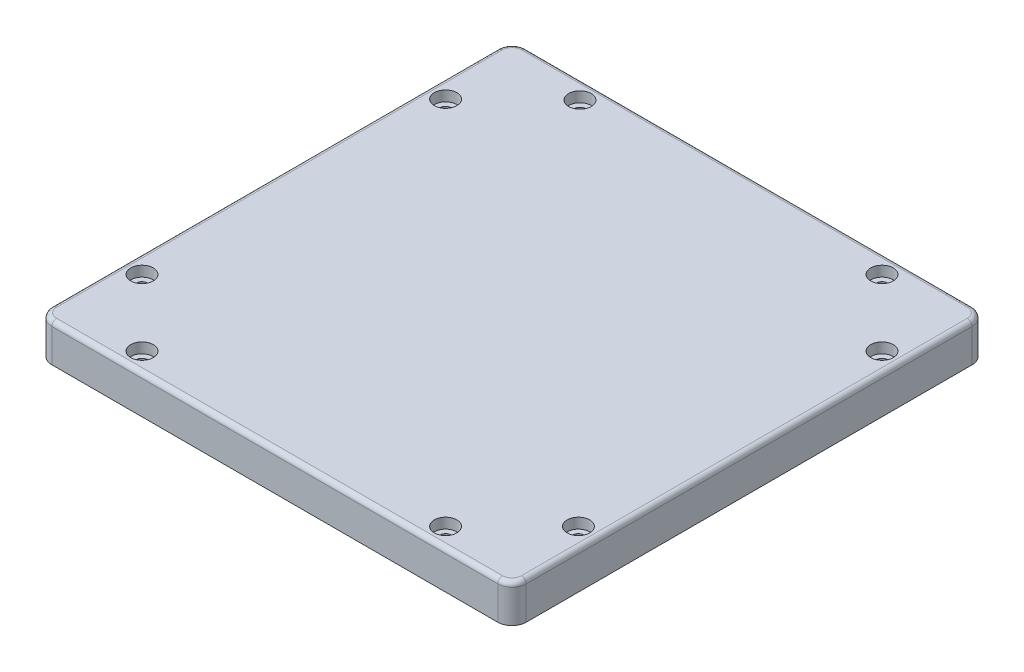
SolidWorks part; units mm, degrees
ref_plane "Front Plane" through (0, 0, 0) normal (0, 0, 1) x (1, 0, 0)
ref_plane "Top Plane" through (0, 0, 0) normal (0, 1, 0) x (1, 0, 0)
ref_plane "Right Plane" through (0, 0, 0) normal (1, 0, 0) x (0, 0, -1)
sketch "Sketch3" plane through (0, 0, 0) normal (0, 1, 0) x (1, 0, 0)
  line L1 (-50, 50) -> (50, 50)
  line L2 (-50, 50) -> (-50, -50)
  line L3 (-50, -50) -> (50, -50)
  line L4 (50, 50) -> (50, -50)
  line L5 (-50, 50) -> (50, -50) construction
  line L6 (-50, -50) -> (50, 50) construction
  point P0 (0, 0)
extrude "Boss-Extrude2" add sketch "Sketch3" along normal blind 8
sketch "Sketch4" plane through (0, 8, 0) normal (0, 1, 0) x (1, 0, 0)
  line L0 (50, -50) -> (-50, 50) construction
  line L1 (-50, 50) -> (50, 50) construction
  line L2 (50, 50) -> (-50, -50) construction
  line L3 (-50, -50) -> (50, -50) construction
  line L4 (-50, -50) -> (-42, -50) construction
  line L5 (-42, -50) -> (-42, 50) construction
  line L6 (50, -50) -> (42, -50) construction
  line L7 (42, -50) -> (42, 50) construction
  line L8 (42, 50) -> (50, 50) construction
  line L9 (50, 50) -> (50, 42) construction
  line L10 (50, 42) -> (-50, 42) construction
  line L11 (50, -50) -> (50, -42) construction
  line L12 (50, -42) -> (-50, -42) construction
  line L13 (-50, 50) -> (-50, -50) construction
  line L14 (50, -46) -> (32, -46) construction
  line L15 (-50, -46) -> (-32, -46) construction
  line L16 (42, -50) -> (50, -50) construction
  line L17 (50, -50) -> (46, -50) construction
  line L18 (46, -50) -> (46, -32) construction
  line L19 (50, 46) -> (32, 46) construction
  line L20 (50, 50) -> (42, 50) construction
  line L21 (42, 50) -> (46, 50) construction
  line L22 (46, 50) -> (46, 32) construction
  line L23 (-50, 50) -> (-42, 50) construction
  line L24 (-42, 50) -> (-46, 50) construction
  line L25 (-46, 50) -> (-46, 32) construction
  line L26 (-50, 42) -> (-50, 50) construction
  line L27 (-50, 50) -> (-50, 46) construction
  line L28 (-42, -50) -> (-50, -50) construction
  line L29 (-50, -50) -> (-46, -50) construction
  line L30 (-46, -50) -> (-46, -32) construction
  line L31 (-49.6798, 46) -> (-31.6798, 46) construction
hole_wizard "CBORE for #2 Socket Head Cap Screw1" positions "3DSketch1" profile "Sketch5" counterbore size "#2" standard "ANSI Inch" end condition through all
sketch3d "3DSketch1"
  line L0 (50, 8, 46) -> (32, 8, 46) construction
  point P0 (-46, 8, 32)
  point P3 (-32, 8, 46)
  point P6 (-46, 8, -32)
  point P9 (-31.6798, 8, -46)
  point P12 (32, 8, -46)
  point P15 (46, 8, -32)
  point P18 (32, 8, 46)
  point P22 (46, 8, 32)
sketch "Sketch5" plane through (-46, 8, 32) normal (1, 0, 0) x (0, 0, 1)
  line L0 (0, 0) -> (0, 8)
  line L1 (0, 8) -> (1.2192, 8)
  line L3 (1.2192, 8) -> (1.2192, 2.1844)
  line L4 (1.2192, 2.1844) -> (2.3812, 2.1844)
  line L5 (2.3812, 2.1844) -> (2.3812, 0)
  line L7 (2.3812, 0) -> (0, 0)
  line L11 (0, -6.35) -> (0, 107.95) construction
  dimension "Thru Hole Dia." = 2.4384
  dimension "Thru Hole Depth" = 8
  dimension "C'Bore Dia." = 4.7625
  dimension "C'Bore Depth" = 2.1844
fillet "Fillet1" radius 1 4 edges at (0, 8, 50) (-50, 8, 0) (0, 8, -50) (50, 8, 0)
fillet "Fillet2" radius 3 6 edges at (-49.7071, 7.7071, -49.7071) (-49.7071, 7.7071, 49.7071) (49.7071, 7.7071, -49.7071) (50, 3.5, -50) (-50, 3.5, 50) (-50, 3.5, -50)
fillet "Fillet3" radius 3 2 edges at (49.7071, 7.7071, 49.7071) (50, 3.5, 50)
